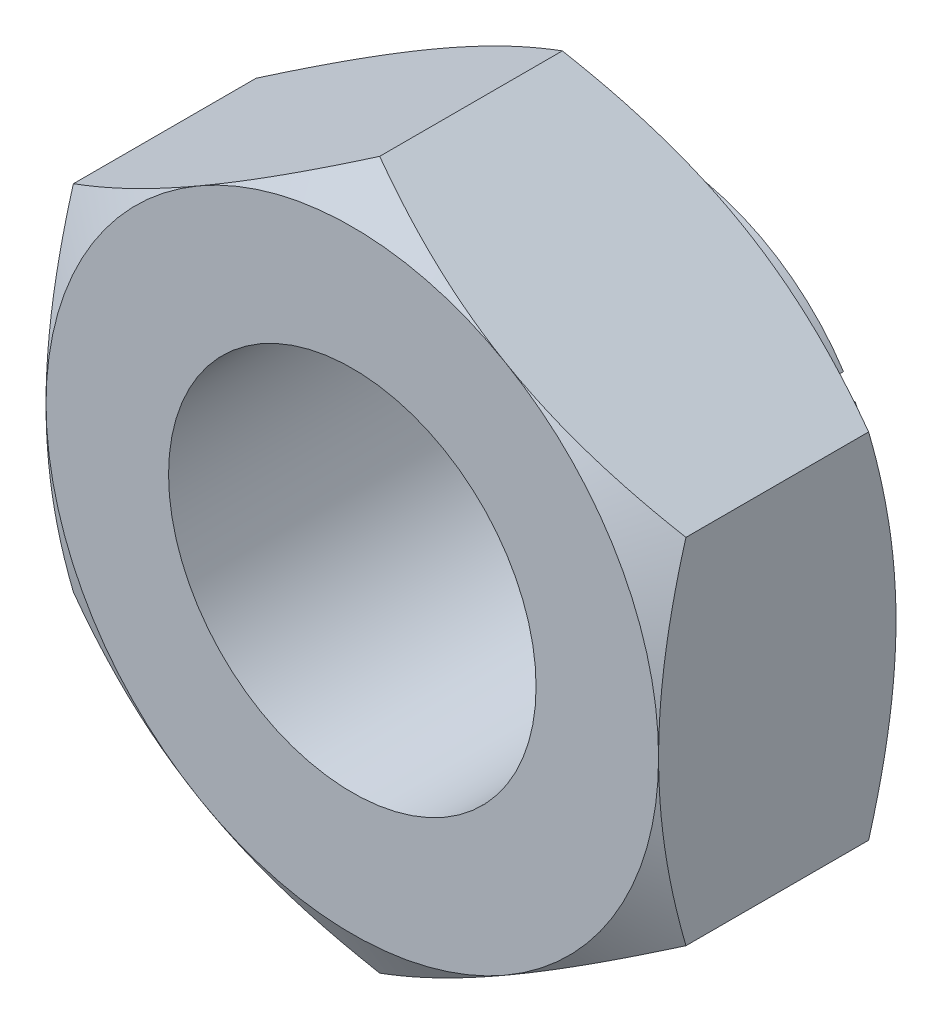
SolidWorks part; units mm, degrees
ref_plane "Front Plane" through (0, 0, 0) normal (0, 0, 1) x (1, 0, 0)
ref_plane "Top Plane" through (0, 0, 0) normal (0, 1, 0) x (1, 0, 0)
ref_plane "Right Plane" through (0, 0, 0) normal (1, 0, 0) x (0, 0, -1)
sketch "Sketch1" plane through (0, 0, 0) normal (0, 0, 1) x (1, 0, 0)
  line L1 (0, 5.7735) -> (-5, 2.8868)
  line L2 (-5, 2.8868) -> (-5, -2.8868)
  line L3 (-5, -2.8868) -> (0, -5.7735)
  line L4 (0, -5.7735) -> (5, -2.8868)
  line L5 (5, -2.8868) -> (5, 2.8868)
  line L6 (5, 2.8868) -> (0, 5.7735)
  circle A0 centre (0, 0) radius 5 construction
  dimension "Hex" = 10
extrude "Extrude1" add sketch "Sketch1" against normal blind 5
sketch "Sketch2" plane through (0, 0, 0) normal (0, 0, 1) x (1, 0, 0)
  circle A0 centre (0, 0) radius 5 construction
  circle A1 centre (0, 0) radius 5
extrude "Cut-Extrude1" cut sketch "Sketch2" against normal through all draft 60 flip side to cut
sketch "Sketch4" plane through (0, 0, 0) normal (0, 0, 1) x (1, 0, 0)
  circle A0 centre (0, 0) radius 3
  dimension "Thread Dia" = 6
extrude "Cut-Extrude3" cut sketch "Sketch4" against normal through all
sketch "Sketch5" [suppressed] plane through (0, 0, 0) normal (0, 0, 1) x (1, 0, 0)
  circle A0 centre (0, 0) radius 3 construction
  circle A1 centre (0, 0) radius 3
sketch "Sketch12" plane through (0, 0, -5) normal (0, 0, -1) x (-1, 0, 0)
  line L0 (0, 0) -> (5, 2.8868) construction
  circle A0 centre (0, 0) radius 3.6
  dimension "D1" = 7.2
extrude "Cut-Extrude10" cut sketch "Sketch12" against normal blind 1.125 flip side to cut
sketch "Sketch15" plane through (0, 0, -5) normal (0, 0, -1) x (-1, 0, 0)
  line L0 (0, 0) -> (0, -5.7735)
extrude "Cut-Extrude-Thin2" cut sketch "Sketch15" against normal offset from surface (0.617 mm away) 0.508 thin up to face at (0, 0, -3.875) thin type mid plane wall 0.381
pattern_circular "CirPattern1" count 6 over 360 of "Cut-Extrude-Thin2"
sketch "Sketch3" plane through (0, 0, -3.875) normal (0, 0, -1) x (-1, 0, 0)
  circle A1 centre (0, 0) radius 5
  circle A2 centre (0, 0) radius 5
  dimension "D1" = 0
extrude "Cut-Extrude2" cut sketch "Sketch3" against normal through all draft 60 flip side to cut
curve "Helix/Spiral1" [suppressed] pitch 1 height 6 turns 6 parameters "pitch"=1
sketch "Sketch9" [suppressed] plane through (0, 0, 0) normal (1, 0, 0) x (0, 0, -1)
  line L0 (-0.5, 2.3505) -> (-0.375, 2.3505)
  line L1 (-0.375, 2.3505) -> (0, 3)
  line L2 (-0.5, 2.3505) -> (-0.875, 3)
  line L3 (-0.875, 3) -> (0, 3)
  line L4 (-0.4375, 2.3505) -> (-0.4375, 3) construction
  line L5 (-0.6875, 2.6752) -> (-0.1875, 2.6752) construction
  line L6 (0, 3) -> (0, -3) construction
  dimension "D1" = 0.125
  dimension "D2" = 0.5
  dimension "D3" = 60
sweep "Sweep1" [suppressed] add profiles "Sketch9" path "Helix/Spiral1"
sketch "Sketch10" [suppressed] plane through (0, 0, 0) normal (0, 0, 1) x (1, 0, 0)
  line L6 (0, 5.7735) -> (-5, 2.8868)
  line L7 (-5, 2.8868) -> (-5, -2.8868)
  line L8 (-5, -2.8868) -> (0, -5.7735)
  line L9 (0, -5.7735) -> (5, -2.8868)
  line L10 (5, -2.8868) -> (5, 2.8868)
  line L11 (5, 2.8868) -> (0, 5.7735)
  line L12 (0, 5.7735) -> (-5, 2.8868)
  line L13 (-5, 2.8868) -> (-5, -2.8868)
  line L14 (-5, -2.8868) -> (0, -5.7735)
  line L15 (0, -5.7735) -> (5, -2.8868)
  line L16 (5, -2.8868) -> (5, 2.8868)
  line L17 (5, 2.8868) -> (0, 5.7735)
  dimension "D1" = 0
extrude "Cut-Extrude8" [suppressed] cut sketch "Sketch10" along normal through all
sketch "Sketch11" [suppressed] plane through (0, 0, -5) normal (0, 0, -1) x (-1, 0, 0)
  line L6 (5, 2.8868) -> (0, 5.7735)
  line L7 (5, -2.8868) -> (5, 2.8868)
  line L8 (0, -5.7735) -> (5, -2.8868)
  line L9 (-5, -2.8868) -> (0, -5.7735)
  line L10 (-5, 2.8868) -> (-5, -2.8868)
  line L11 (0, 5.7735) -> (-5, 2.8868)
  line L12 (5, 2.8868) -> (0, 5.7735)
  line L13 (5, -2.8868) -> (5, 2.8868)
  line L14 (0, -5.7735) -> (5, -2.8868)
  line L15 (-5, -2.8868) -> (0, -5.7735)
  line L16 (-5, 2.8868) -> (-5, -2.8868)
  line L17 (0, 5.7735) -> (-5, 2.8868)
  dimension "D1" = 0
extrude "Cut-Extrude9" [suppressed] cut sketch "Sketch11" along normal through all
sketch "Sketch7" [suppressed] plane through (0, 0, 0) normal (0, 0, 1) x (1, 0, 0)
  circle A1 centre (0, 0) radius 3
  circle A2 centre (0, 0) radius 3
  dimension "D1" = 0
extrude "Cut-Extrude6" [suppressed] cut sketch "Sketch7" against normal through all draft 45
sketch "Sketch8" [suppressed] plane through (0, 0, -5) normal (0, 0, -1) x (-1, 0, 0)
  circle A1 centre (0, 0) radius 3
  circle A3 centre (0, 0) radius 3
  dimension "D1" = 0
extrude "Cut-Extrude7" [suppressed] cut sketch "Sketch8" against normal through all draft 45
sketch "Sketch17" [suppressed] plane through (0, 0, 0) normal (0, 0, 1) x (1, 0, 0)
  circle A0 centre (0, 0) radius 3.01
  circle A1 centre (0, 0) radius 3
  circle A2 centre (0, 0) radius 3
  dimension "D1" = 0
  dimension "D2" = 0.01
extrude "Boss-Extrude1" [suppressed] add sketch "Sketch17" against normal blind 0.1
sketch "Sketch16" [suppressed] plane through (0, 0, -5) normal (0, 0, -1) x (-1, 0, 0)
  line L1 (0, 0) -> (0, -5.7735)
extrude "Cut-Extrude-Thin3" [suppressed] cut sketch "Sketch16" against normal offset from surface (0.625 mm away) 0.5 thin thin type mid plane wall 0.381
pattern_circular "CirPattern14" [suppressed] count 6 over 360 of bodies 126
ref_axis "Center Axis 1" through (0, 0, -5.4129) along (0, 0, 1)
equation "\"D2@Sketch9\" = \"pitch@Helix/Spiral1\"*.5"
equation "\"D3@Helix/Spiral1\" = \"pitch@Helix/Spiral1\"+\"Height@Extrude1\""
equation "\"D1@Sketch9\" = \"pitch@Helix/Spiral1\"*.125"
equation "\"D1@Sketch12\" = \"Thread Dia@Sketch4\"*1.2"
equation "\"D1@Cut-Extrude10\" = \"Height@Extrude1\"*.225"
